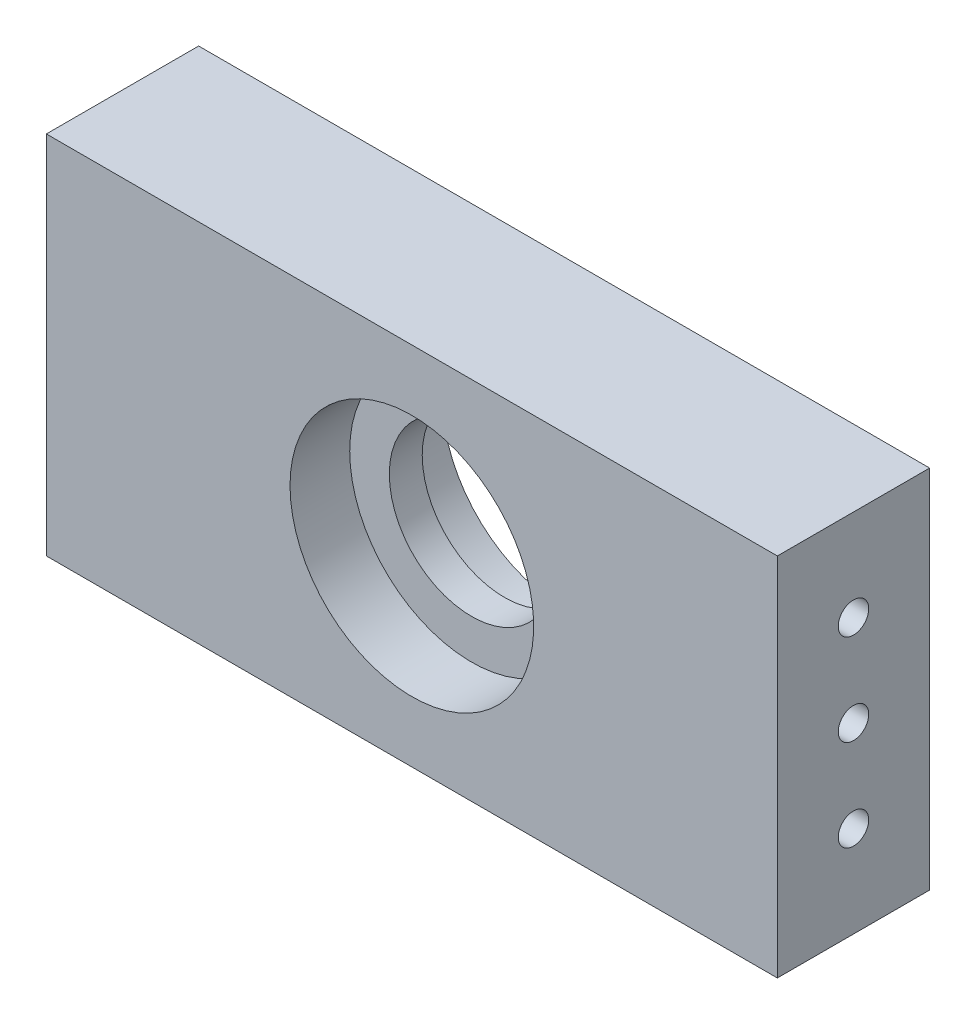
SolidWorks part; units mm, degrees
material "1060 Alloy"
ref_plane "Front Plane" through (0, 0, 0) normal (0, 0, 1) x (1, 0, 0)
ref_plane "Top Plane" through (0, 0, 0) normal (0, 1, 0) x (1, 0, 0)
ref_plane "Right Plane" through (0, 0, 0) normal (1, 0, 0) x (0, 0, -1)
sketch "Sketch1" plane through (0, 0, 0) normal (0, 0, 1) x (1, 0, 0)
  line L1 (0, 0) -> (152.4, 0)
  line L2 (0, 0) -> (0, 76.2)
  line L3 (0, 76.2) -> (152.4, 76.2)
  line L4 (152.4, 0) -> (152.4, 76.2)
  dimension "D1" = 152.4
  dimension "D2" = 76.2
extrude "Boss-Extrude1" add sketch "Sketch1" along normal blind 31.75
sketch "Sketch2" plane through (0, 0, 0) normal (0, 0, -1) x (-1, 0, 0)
  line L0 (0, 38.1) -> (-152.4, 38.1) construction
  line L1 (0, 76.2) -> (0, 0) construction
  line L2 (-152.4, 0) -> (-152.4, 76.2) construction
  line L4 (-152.4, 76.2) -> (0, 76.2) construction
  line L5 (-76.2, 76.2) -> (-76.2, 0) construction
  line L6 (0, 0) -> (-152.4, 0) construction
  circle A0 centre (-76.2, 38.1) radius 25.4
  circle A1 centre (-76.2, 38.1) radius 17.145
  dimension "D1" = 50.8
  dimension "D2" = 34.29
extrude "Cut-Extrude1" cut sketch "Sketch2" against normal through all contours A1
extrude "Cut-Extrude3" cut sketch "Sketch2<2>" against normal blind 12.446
sketch "Sketch2<2>" plane through (0, 0, 0) normal (0, 0, -1) x (-1, 0, 0) same geometry as "Sketch2"
ref_plane "Plane2" through (0, 0, 15.875) normal (0, 0, -1) x (-1, 0, 0)
mirror "Mirror2" about plane through (0, 0, 15.875) normal (0, 0, -1) of "Cut-Extrude3"
sketch "Sketch3" plane through (152.4, 0, 0) normal (1, 0, 0) x (0, 0, -1)
  line L0 (-15.875, -41.91) -> (-15.875, 41.91) construction
  line L1 (-31.75, 76.2) -> (0, 76.2) construction
  line L5 (-31.75, 0) -> (0, 0) construction
  circle A0 centre (-15.875, 57.15) radius 3.175
  circle A1 centre (-15.875, 19.05) radius 3.175
  circle A2 centre (-15.875, 38.1) radius 3.175
  point P8 (-15.875, 13.3757)
  point P9 (-15.875, 34.8853)
  point P10 (-15.875, 60.1356)
  dimension "D1" = 6.35
  dimension "D2" = 19.05
  dimension "D3" = 19.05
  dimension "D4" = 19.05
extrude "Cut-Extrude4" cut sketch "Sketch3" against normal blind 31.75
equation "\"through_diamiter\"= 1.35"
equation "\"D2@Sketch2\"=\"through_diamiter\""
equation "\"bearing depth\"= 0.5"
